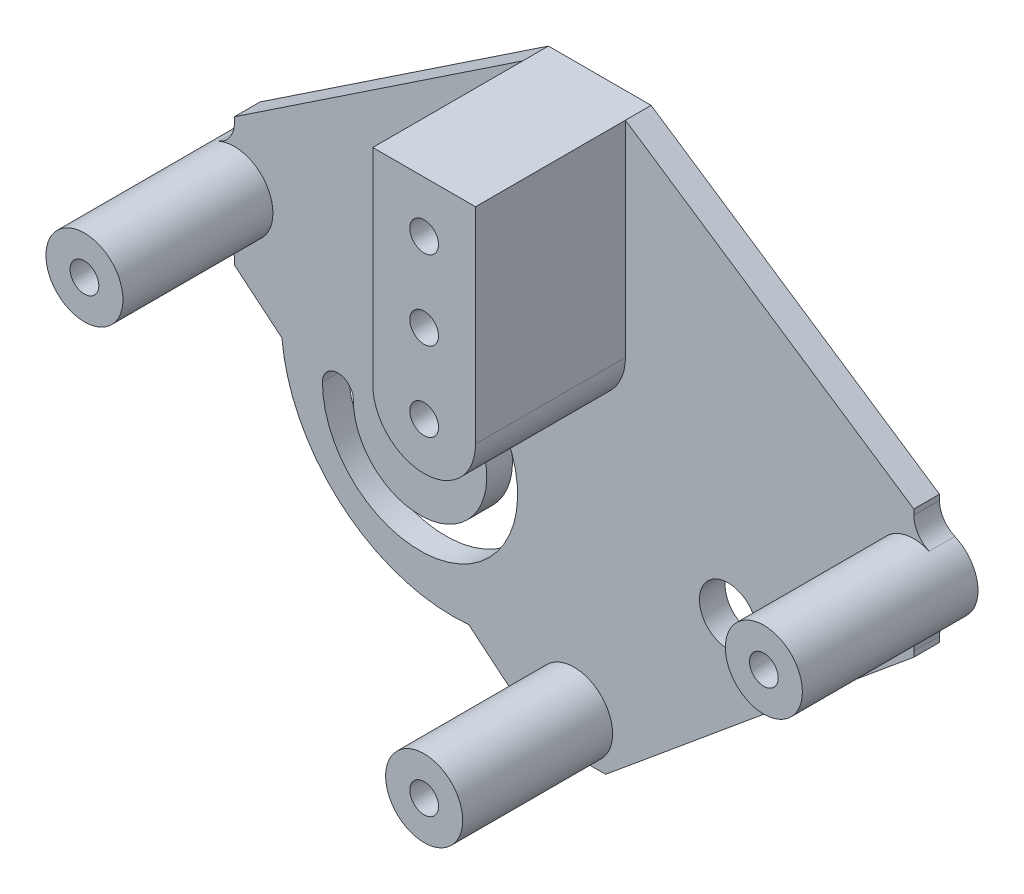
SolidWorks part; units mm, degrees
ref_plane "Front" through (0, 0, 0) normal (0, 0, 1) x (1, 0, 0)
ref_plane "Top" through (0, 0, 0) normal (0, 1, 0) x (1, 0, 0)
ref_plane "Right" through (0, 0, 0) normal (1, 0, 0) x (0, 0, -1)
sketch "Sketch1" plane through (0, 0, 0) normal (0, 0, 1) x (1, 0, 0)
  line L1 (0, 0) -> (84.008, 0)
  line L2 (0, 0) -> (0, 71.2724)
  line L3 (0, 71.2724) -> (84.008, 71.2724)
  line L4 (84.008, 0) -> (84.008, 71.2724)
  dimension "D1" = 84.008
  dimension "D2" = 71.2724
extrude "Boss-Extrude1" add sketch "Sketch1" along normal blind 3.175
sketch "Sketch5" plane through (0, 0, 3.175) normal (0, 0, 1) x (1, 0, 0)
  line L0 (84.008, 0) -> (84.008, 71.2724) construction
  line L1 (0, 71.2724) -> (0, 0) construction
  line L2 (0, 0) -> (84.008, 0) construction
  circle A0 centre (84.008, 39.525) radius 4.7625
  circle A1 centre (0, 39.525) radius 4.7625
  dimension "D1" = 39.525
  dimension "D3" = 9.525
  dimension "D4" = 9.525
  dimension "D2" = 39.525
extrude "Boss-Extrude3" add sketch "Sketch5" against normal up to surface (3.175 mm away) up to face at (42.004, 35.6362, 0)
sketch "Sketch3" plane through (0, 0, 3.175) normal (0, 0, 1) x (1, 0, 0)
  line L0 (0, 0) -> (84.008, 0) construction
  circle A0 centre (42.004, 4.7625) radius 1.8415
  point P4 (42.004, 0)
  dimension "D1" = 3.683
  dimension "D2" = 4.7625
extrude "Cut-Extrude1" cut sketch "Sketch3" against normal through all
sketch "Sketch6" plane through (0, 0, 3.175) normal (0, 0, 1) x (1, 0, 0)
  line L1 (35.654, 71.2724) -> (48.354, 71.2724)
  line L2 (35.654, 71.2724) -> (35.654, 45.8724)
  line L4 (48.354, 71.2724) -> (48.354, 45.8724)
  line L5 (84.008, 71.2724) -> (0, 71.2724) construction
  circle A0 centre (84.008, 39.525) radius 4.7625
  circle A1 centre (0, 39.525) radius 4.7625
  circle A2 centre (42.004, 4.7625) radius 4.7625
  arc A3 (48.354, 45.8724) -> (35.654, 45.8724) centre (42.004, 45.8724) cw
  point P10 (42.004, 39.5224)
  point P13 (42.004, 71.2724)
  point P16 (42.004, 71.2724)
  dimension "D1" = 9.525
  dimension "D2" = 9.525
  dimension "D3" = 9.525
  dimension "D6" = 6.35
  dimension "D4" = 12.7
  dimension "D5" = 31.75
extrude "Boss-Extrude4" add sketch "Sketch6" along normal blind 18.542
sketch "Sketch4" plane through (0, 0, 3.175) normal (0, 0, 1) x (1, 0, 0)
  line L1 (84.008, 71.2724) -> (48.354, 71.2724) construction
  line L2 (84.008, 71.2724) -> (0, 71.2724) construction
  circle A0 centre (42.004, 64.9224) radius 1.778
  circle A1 centre (42.004, 55.1434) radius 1.778
  circle A2 centre (42.004, 45.3644) radius 1.778
  point P8 (42.004, 71.2724)
  dimension "D1" = 3.556
  dimension "D2" = 6.35
  dimension "D3" = 19.558
  dimension "D4" = 9.779
extrude "Cut-Extrude2" cut sketch "Sketch4" along normal through all both and the other way through all
sketch "Sketch7" plane through (0, 0, 0) normal (0, 0, -1) x (-1, 0, 0)
  circle A0 centre (-42.004, 4.7625) radius 1.778
  circle A1 centre (0, 39.525) radius 1.778
  circle A2 centre (-84.008, 39.525) radius 1.778
  dimension "D1" = 3.556
extrude "Cut-Extrude3" cut sketch "Sketch7" against normal through all
sketch "Sketch8" plane through (0, 0, 0) normal (0, 0, -1) x (-1, 0, 0)
  circle A0 centre (-61.054, 24.525) radius 3.556
  circle A1 centre (-22.954, 24.525) radius 3.4925
  circle A2 centre (-42.004, 4.7625) radius 1.8415 construction
  dimension "D1" = 38.1
  dimension "D2" = 7.112
  dimension "D3" = 6.985
  dimension "D5" = 19.7625
  dimension "D6" = 19.7625
  dimension "D4" = 19.05
extrude "Cut-Extrude4" cut sketch "Sketch8" against normal through all
sketch "Sketch9" plane through (0, 0, 0) normal (0, 0, -1) x (-1, 0, 0)
  line L0 (-84.008, 0) -> (-84.008, 31.5875)
  line L1 (-84.008, 0) -> (-84.008, 34.7625) construction
  line L2 (-84.008, 31.5875) -> (-45.908, 0)
  line L3 (0, 0) -> (-84.008, 0) construction
  line L4 (-45.908, 0) -> (-84.008, 0)
  line L5 (-84.008, 71.2724) -> (-84.008, 47.4625)
  line L6 (-84.008, 44.2875) -> (-84.008, 71.2724) construction
  line L7 (-84.008, 47.4625) -> (-48.354, 71.2724)
  line L8 (-48.354, 71.2724) -> (-84.008, 71.2724)
  dimension "D1" = 38.1
  dimension "D2" = 3.175
  dimension "D3" = 3.175
extrude "Cut-Extrude5" cut sketch "Sketch9" against normal through all
ref_plane "Plane1" through (42.004, 0, 0) normal (1, 0, 0) x (0, 0, -1)
mirror "Mirror1" about plane through (42.004, 0, 0) normal (1, 0, 0) of "Cut-Extrude5"
fillet "Fillet1" radius 3.175 4 edges at (0, 34.7625, 1.5875) (0, 44.2875, 1.5875) (84.008, 44.2875, 1.5875) (84.008, 34.7625, 1.5875)
sketch "Sketch10" plane through (0, 0, 0) normal (0, 0, -1) x (-1, 0, 0)
  line L0 (-38.1, 0) -> (0, 31.5875) construction
  line L1 (-28.9756, 7.5647) -> (-5.8739, 26.7176)
  arc A0 (-27.6936, 33.5117) -> (-12.9642, 22.673) centre (-22.954, 24.525) ccw construction
  arc A1 (-28.5823, 35.1967) -> (-11.0911, 22.3257) centre (-22.954, 24.525) ccw
  arc A2 (-26.805, 31.8267) -> (-14.8373, 23.0202) centre (-22.954, 24.525) ccw
  arc A3 (-26.805, 31.8267) -> (-28.5823, 35.1967) centre (-27.6936, 33.5117) ccw
  arc A4 (-11.0911, 22.3257) -> (-14.8373, 23.0202) centre (-12.9642, 22.673) ccw
  arc A5 (-28.9756, 7.5647) -> (-5.8739, 26.7176) centre (-27.0012, 28.692) ccw
  point P4 (-28.9756, 16.3418)
  line M10 (-38.1, 0) -> (0, 31.5875)
  dimension "D1" = 10.16
  dimension "D2" = 3.81
extrude "Boss-Extrude5" add sketch "Sketch10" against normal blind 3.175 contours A5 A4 A1 M10 region at (15.6548, 14.7848, 0)
sketch "Sketch11" plane through (0, 0, 0) normal (0, 0, -1) x (-1, 0, 0)
  arc A0 (-26.5794, 34.0161) -> (-12.794, 24.525) centre (-22.954, 24.525) ccw construction
  arc A1 (-27.2592, 35.7957) -> (-10.889, 24.525) centre (-22.954, 24.525) ccw
  arc A2 (-25.8996, 32.2366) -> (-14.699, 24.525) centre (-22.954, 24.525) ccw
  arc A3 (-25.8996, 32.2366) -> (-27.2592, 35.7957) centre (-26.5794, 34.0161) ccw
  arc A4 (-10.889, 24.525) -> (-14.699, 24.525) centre (-12.794, 24.525) ccw
  arc A5 (-21.6189, 34.5969) -> (-12.794, 24.525) centre (-22.954, 24.525) ccw construction
  arc A6 (-21.3686, 36.4854) -> (-10.889, 24.525) centre (-22.954, 24.525) ccw
  arc A7 (-21.8692, 32.7084) -> (-14.699, 24.525) centre (-22.954, 24.525) ccw
  arc A8 (-21.8692, 32.7084) -> (-21.3686, 36.4854) centre (-21.6189, 34.5969) ccw
  arc A9 (-10.889, 24.525) -> (-14.699, 24.525) centre (-12.794, 24.525) ccw
  point P4 (-28.7155, 16.1566)
  point P12 (-30.5956, 17.8294)
  line M31 (-23.0704, 12.4606) -> (-11.0785, 22.4027)
  arc M32 (-11.0785, 22.4027) -> (-11.0911, 22.3257) centre (-12.9642, 22.673) cw
  dimension "D1" = 10.16
  dimension "D2" = 3.81
  dimension "D3" = 10.16
  dimension "D4" = 3.81
extrude "Cut-Extrude7" cut sketch "Sketch11" against normal blind 5.08 contours A1 A4 A2 A3 M31 M32 | A7 A8 A6 A3 region at (25.1142, 34.5758, 0) region at (22.6525, 34.6849, 0)
